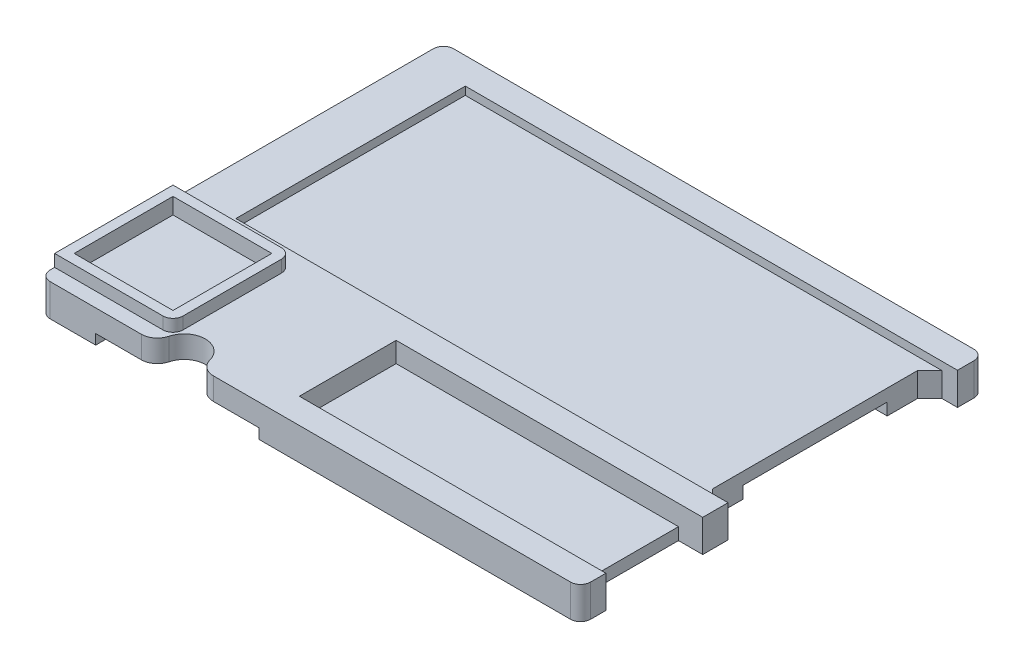
SolidWorks part; units mm, degrees
ref_plane "Front Plane" through (0, 0, 0) normal (0, 0, 1) x (1, 0, 0)
ref_plane "Top Plane" through (0, 0, 0) normal (0, 1, 0) x (1, 0, 0)
ref_plane "Right Plane" through (0, 0, 0) normal (1, 0, 0) x (0, 0, -1)
sketch "Sketch1" plane through (0, 0, 0) normal (0, 1, 0) x (1, 0, 0)
  line L1 (-33.5, 17.5) -> (33.5, 17.5)
  line L2 (-33.5, 17.5) -> (-33.5, -17.5)
  line L3 (-33.5, -17.5) -> (33.5, -17.5)
  line L4 (33.5, 17.5) -> (33.5, -17.5)
  line L5 (-33.5, 17.5) -> (33.5, -17.5) construction
  line L6 (-33.5, -17.5) -> (33.5, 17.5) construction
  point P0 (0, 0)
  dimension "D1" = 35
  dimension "D2" = 67
extrude "Boss-Extrude1" add sketch "Sketch1" along normal blind 4
sketch "Sketch2" plane through (0, 4, 0) normal (0, 1, 0) x (1, 0, 0)
  line L0 (-27.51, 14.22) -> (27.4193, 14.22)
  line L1 (-27.26, 13.97) -> (27.1922, 13.97) construction
  line L2 (-27.26, 13.97) -> (-27.26, -13.97) construction
  line L3 (-27.26, -13.97) -> (29.89, -13.97) construction
  line L6 (-27.51, -14.22) -> (30.1653, -14.22)
  line L7 (-27.51, 14.22) -> (-27.51, -14.22)
  line L13 (27.4193, 14.22) -> (33.5, 14.22)
  line L15 (30.1653, -14.22) -> (33.5, -14.22)
  line L16 (33.5, 14.22) -> (33.5, -14.22)
  line L17 (33.5, -17.5) -> (33.5, 17.5) construction
  line L18 (27.1922, 13.97) -> (29.89, -13.97) construction
  line L19 (27.4193, 14.22) -> (30.1653, -14.22) construction
  dimension "D1" = 0.25
extrude "Cut-Extrude1" cut sketch "Sketch2" against normal blind 1
sketch "Sketch3" plane through (0, 4, 0) normal (0, 1, 0) x (1, 0, 0)
  line L0 (-33.5, -17.5) -> (33.5, -17.5) construction
  line L1 (-33.5, -17.5) -> (33.5, -17.5)
  line L2 (-33.5, -17.5) -> (-33.5, -32.5)
  line L3 (-33.5, -32.5) -> (33.5, -32.5)
  line L4 (33.5, -17.5) -> (33.5, -32.5)
  line L5 (0, -32.5) -> (0, 17.5) construction
  line L6 (33.5, 17.5) -> (-33.5, 17.5) construction
  line L7 (-33.5, 17.5) -> (-33.5, -17.5) construction
  dimension "D2" = 15
extrude "Boss-Extrude2" add sketch "Sketch3" against normal blind 4
sketch "Sketch4" plane through (0, 4, 0) normal (0, 1, 0) x (1, 0, 0)
  line L5 (33.5, -32.5) -> (33.5, -14.22) construction
  line L6 (33.5, -17.36) -> (-4.5, -17.36)
  line L8 (33.5, -17.36) -> (33.5, -29.36)
  line L9 (33.5, -29.36) -> (-4.5, -29.36)
  line L10 (-4.5, -17.36) -> (-4.5, -29.36)
  line L11 (-27.51, -14.22) -> (-27.51, -32.5) construction
  line L12 (-33.5, -32.5) -> (33.5, -32.5) construction
  line L13 (-27.51, -23.36) -> (-4.5, -23.36) construction
  dimension "D1" = 38
  dimension "D2" = 12
extrude "Cut-Extrude2" cut sketch "Sketch4" against normal blind 10
sketch "Sketch5" plane through (0, 0, 0) normal (0, -1, 0) x (1, 0, 0)
  line L1 (-4.5, 29.36) -> (30.5, 29.36)
  line L2 (-4.5, 29.36) -> (-4.5, 17.36)
  line L3 (-4.5, 17.36) -> (30.5, 17.36)
  line L4 (30.5, 29.36) -> (30.5, 17.36)
  line L5 (-4.5, 17.36) -> (-4.5, 29.36) construction
  line L6 (-4.5, 29.36) -> (33.5, 29.36) construction
  line L7 (33.5, 17.36) -> (-4.5, 17.36) construction
  point P7 (0, 0)
  dimension "D1" = 35
sketch "Sketch7" plane through (0, 3, 0) normal (0, 1, 0) x (1, 0, 0)
  line L0 (-27.51, -14.22) -> (33.5, -14.22) construction
  line L1 (33.5, 14.22) -> (30.0583, 14.22)
  line L2 (33.5, 14.22) -> (33.5, -14.22)
  line L3 (33.5, -14.22) -> (30.0583, -14.22)
  line L4 (30.0583, 14.22) -> (30.0583, -14.22)
extrude "Cut-Extrude3" cut sketch "Sketch7" against normal blind 10
chamfer "Chamfer1" distance 1.5 angle 45 2 edges at (30.0583, 1.5, 14.22) (30.0583, 1.5, -14.22)
sketch "Sketch8" plane through (0, 0, 0) normal (0, -1, 0) x (1, 0, 0)
  line L0 (30.0583, 8.7) -> (1.7583, 8.7) construction
  line L1 (30.0583, -12.72) -> (30.0583, 12.72) construction
  line L2 (30.0583, 8.7) -> (1.7583, 8.7) construction
  line L3 (1.7583, 8.7) -> (1.7583, 6.7) construction
  line L4 (3.7583, 4.7) -> (3.7583, -4.7) construction
  line L5 (3.7583, 4.7) -> (3.7583, -4.7) construction
  line L6 (3.7583, 0) -> (30.0583, 0) construction
  line L7 (1.7583, -8.7) -> (1.7583, -6.7) construction
  line L8 (30.0583, -8.7) -> (1.7583, -8.7) construction
  line L9 (30.0583, 8.7) -> (30.0583, -8.7) construction
  line L24 (30.0583, 8.95) -> (1.5083, 8.95)
  line L25 (1.5083, 8.95) -> (1.5083, 6.4321)
  line L26 (3.5083, 4.7) -> (3.5083, -4.7)
  line L27 (1.5083, -8.95) -> (1.5083, -6.4321)
  line L28 (30.0583, -8.95) -> (1.5083, -8.95)
  line L29 (30.0583, 8.95) -> (30.0583, -8.95)
  arc A0 (1.7583, 6.7) -> (3.7583, 4.7) centre (1.7583, 4.7) cw construction
  arc A1 (1.7583, -6.7) -> (3.7583, -4.7) centre (1.7583, -4.7) ccw construction
  arc A6 (1.5083, 6.4321) -> (3.5083, 4.7) centre (1.7583, 4.7) cw
  arc A7 (1.5083, -6.4321) -> (3.5083, -4.7) centre (1.7583, -4.7) ccw
  dimension "D1" = 0.25
extrude "Cut-Extrude4" cut sketch "Sketch8" against normal blind 1.5
extrude "Boss-Extrude4" add sketch "Sketch5" against normal blind 1.5
sketch "Sketch9" plane through (0, 0, 0) normal (0, -1, 0) x (1, 0, 0)
  line L1 (-26.605, 31.6614) -> (-6.355, 31.6614)
  line L2 (-26.605, 31.6614) -> (-26.605, 11.4114)
  line L3 (-26.605, 11.4114) -> (-6.355, 11.4114)
  line L4 (-6.355, 31.6614) -> (-6.355, 11.4114)
  circle A0 centre (-26.605, 21.5364) radius 1.925
  circle A1 centre (-6.355, 21.5364) radius 1.925
  dimension "D3" = 3.85
  dimension "D4" = 3.85
  dimension "D1" = 20.25
  dimension "D2" = 20.25
extrude "Cut-Extrude5" cut sketch "Sketch9" against normal blind 1.25 contours A1 L4 L1 L2 A0 L3 | L2 A0 | L4 A1 | L4 A1 | L2 A0 region at (-16.48, 0, 21.5364) region at (-25.788, 0, 21.5364) region at (-27.422, 0, 21.5364) region at (-5.538, 0, 21.5364) region at (-7.172, 0, 21.5364)
sketch "Sketch10" plane through (0, 1.25, 0) normal (0, -1, 0) x (1, 0, 0)
  circle A0 centre (-16.48, 31.6614) radius 2.625
  dimension "D1" = 5.25
extrude "Cut-Extrude6" cut sketch "Sketch10" against normal blind 6.6 and the other way blind 6.6
fillet "Fillet4" radius 2 2 edges at (-13.9925, 2, 32.5) (-18.9674, 2, 32.5)
sketch "Sketch11" plane through (0, 4, 0) normal (0, 1, 0) x (1, 0, 0)
  line L1 (-32.2875, -17.235) -> (-20.0375, -17.235)
  line L2 (-32.2875, -17.235) -> (-32.2875, -29.485)
  line L3 (-32.2875, -29.485) -> (-20.0375, -29.485)
  line L4 (-20.0375, -17.235) -> (-20.0375, -29.485)
  line L5 (-32.2875, -17.235) -> (-20.0375, -29.485) construction
  line L6 (-32.2875, -29.485) -> (-20.0375, -17.235) construction
  line L7 (-26.1625, -23.36) -> (-4.5, -23.36) construction
  line L8 (-4.5, -17.36) -> (-4.5, -29.36) construction
  point P0 (-26.1625, -23.36)
  dimension "D1" = 12.25
  dimension "D2" = 12.25
extrude "Cut-Extrude8" cut sketch "Sketch11" against normal blind 0.5 contours L1 L4 L3 L2
sketch "Sketch13" plane through (0, 4, 0) normal (0, 1, 0) x (1, 0, 0)
  line L0 (-20.0375, -17.235) -> (-20.0375, -29.485) construction
  line L1 (-32.2875, -29.485) -> (-20.0375, -29.485) construction
  line L2 (-32.2875, -17.235) -> (-32.2875, -29.485) construction
  line L3 (-32.2875, -17.235) -> (-20.0375, -17.235) construction
  line L4 (-20.0375, -17.235) -> (-20.0375, -29.485)
  line L5 (-32.2875, -29.485) -> (-20.0375, -29.485)
  line L6 (-32.2875, -17.235) -> (-32.2875, -29.485)
  line L7 (-32.2875, -17.235) -> (-20.0375, -17.235)
  line L8 (-18.8251, -16.0225) -> (-18.8251, -30.6975)
  line L9 (-33.5, -30.6975) -> (-18.8251, -30.6975)
  line L10 (-33.5, -16.0225) -> (-33.5, -30.6975)
  line L11 (-33.5, -16.0225) -> (-18.8251, -16.0225)
  line L12 (-33.5, 17.5) -> (-33.5, -32.5) construction
extrude "Boss-Extrude5" add sketch "Sketch13" along normal blind 1.5
fillet "Fillet5" radius 1.25 2 edges at (-18.8251, 4.75, 16.0225) (-18.8251, 4.75, 30.6975)
fillet "Fillet6" radius 1.25 4 edges at (33.5, 2, 32.5) (33.5, 2, -17.5) (-33.5, 2, 32.5) (-33.5, 2, -17.5)
sketch "Sketch14" plane through (0, 1.25, 0) normal (0, -1, 0) x (1, 0, 0)
  line L2 (-26.605, 31.6614) -> (-6.355, 31.6614)
  line L3 (-26.605, 31.6614) -> (-26.605, 33.3133)
  line L4 (-26.605, 33.3133) -> (-6.355, 33.3133)
  line L5 (-6.355, 31.6614) -> (-6.355, 33.3133)
extrude "Cut-Extrude9" cut sketch "Sketch14" along normal blind 1.5
